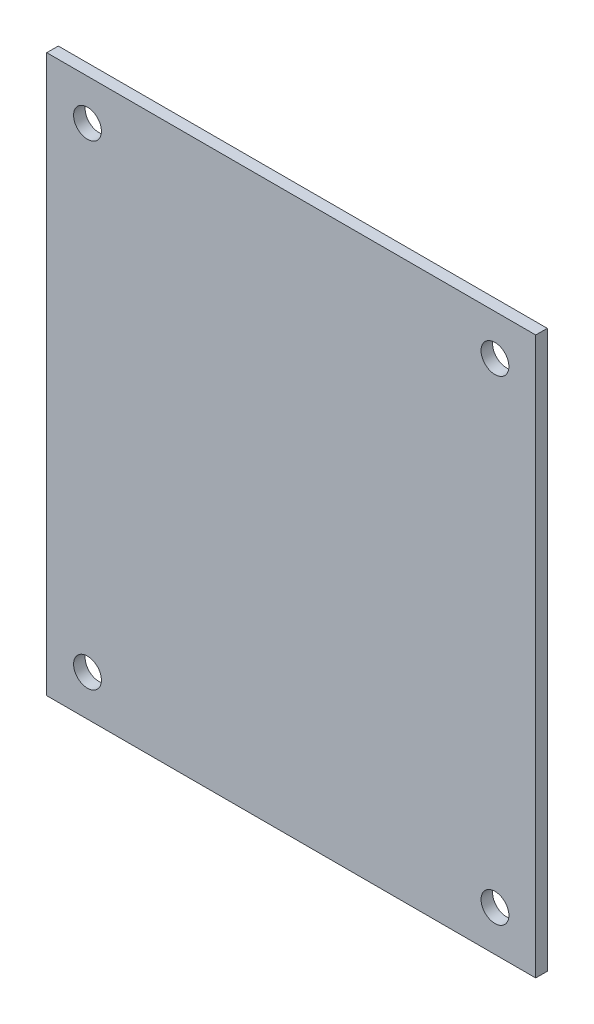
SolidWorks part; units mm, degrees
ref_plane "Front Plane" through (0, 0, 0) normal (0, 0, 1) x (1, 0, 0)
ref_plane "Top Plane" through (0, 0, 0) normal (0, 1, 0) x (1, 0, 0)
ref_plane "Right Plane" through (0, 0, 0) normal (1, 0, 0) x (0, 0, -1)
sketch "Sketch1" plane through (0, 0, 0) normal (0, 0, 1) x (1, 0, 0)
  line L1 (-36, 41) -> (36, 41)
  line L2 (-36, 41) -> (-36, -41)
  line L3 (-36, -41) -> (36, -41)
  line L4 (36, 41) -> (36, -41)
  point P4 (0, 41)
  point P5 (-36, 0)
  point P6 (-60.8905, 21.591)
  dimension "D1" = 72
  dimension "D2" = 82
extrude "Boss-Extrude1" add sketch "Sketch1" along normal blind 1.7
sketch "Sketch2" plane through (0, 0, 1.7) normal (0, 0, 1) x (1, 0, 0)
  line L0 (-36, 41) -> (-36, -41) construction
  line L1 (36, 41) -> (-36, 41) construction
  circle A0 centre (-30, 35) radius 2.05
  circle A1 centre (30, 35) radius 2.05
  circle A2 centre (30, -35) radius 2.05
  circle A3 centre (-30, -35) radius 2.05
  dimension "D3" = 4.1
  dimension "D1" = 6
  dimension "D2" = 6
  dimension "D4" = 2
  dimension "D5" = 2
extrude "Cut-Extrude1" cut sketch "Sketch2" against normal through all
